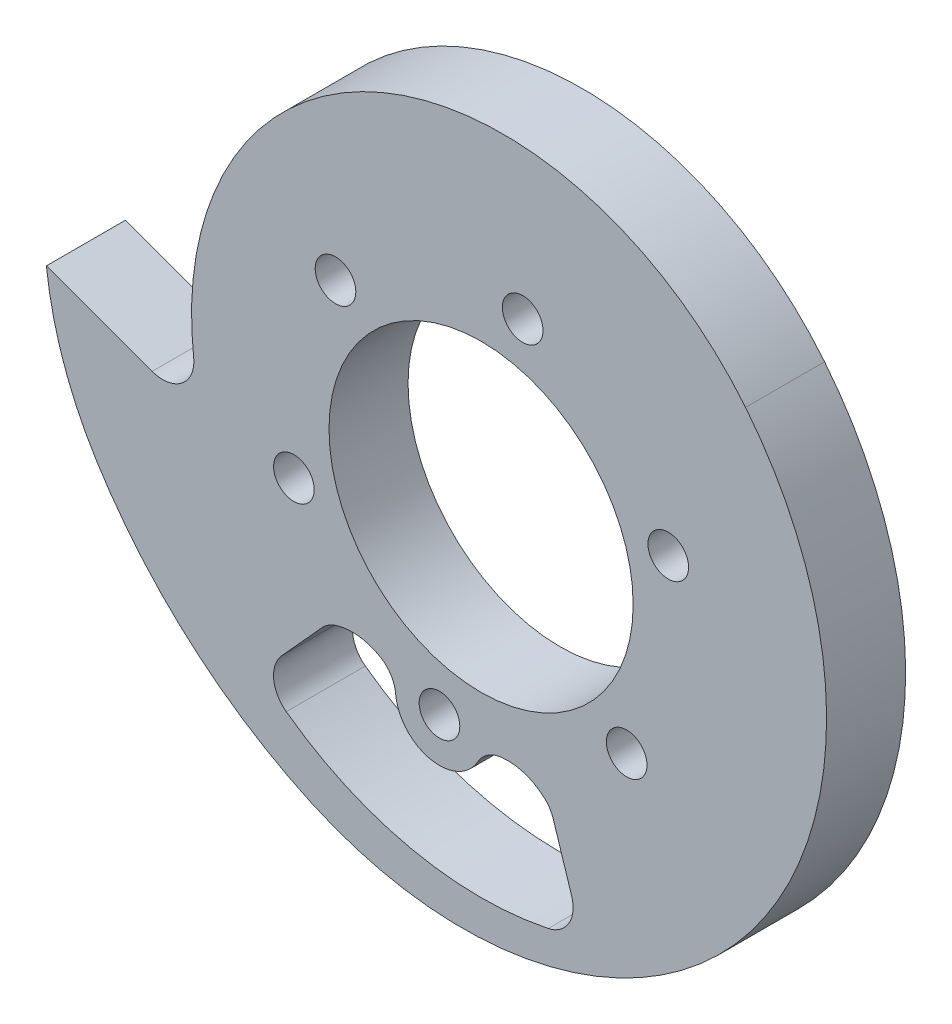
SolidWorks part; units mm, degrees
material "AR500 Weight at A2 Tool Steel Prop."
ref_plane "Front Plane" through (0, 0, 0) normal (0, 0, 1) x (1, 0, 0)
ref_plane "Top Plane" through (0, 0, 0) normal (0, 1, 0) x (1, 0, 0)
ref_plane "Right Plane" through (0, 0, 0) normal (1, 0, 0) x (0, 0, -1)
other "Center of Mass"
sketch "Sketch1" plane through (0, 0, 0) normal (0, 0, 1) x (1, 0, 0)
  line L0 (-69.85, 0) -> (-44.4783, -9.2345)
  line L1 (0, 0) -> (-61.8777, -22.9731) construction
  line L2 (-44.4783, -9.2345) -> (0, 0) construction
  line L3 (-27.2394, -53.4604) -> (0, 0) construction
  line L4 (42.4942, 36.4725) -> (0, 0) construction
  line L5 (0, 0) -> (-25.1554, 0) construction
  line L7 (-69.85, 0) -> (-69.5019, -2.1981) construction
  line L8 (-69.85, 0) -> (-69.85, 19.8503) construction
  line L9 (42.4942, 36.4725) -> (53.0039, 45.4929) construction
  circle A0 centre (0, 0) radius 69.85 construction
  circle A1 centre (0, 0) radius 44.45 construction
  circle A3 centre (0, 0) radius 21.4376 construction
  arc A4 (-69.85, 0) -> (-61.8777, -22.9731) centre (-15.0447, 6.1491) ccw
  arc A6 (-27.2394, -53.4604) -> (42.4942, 36.4725) centre (-2.927, -0.3101) ccw
  arc A8 (-44.4783, -9.2345) -> (42.4942, 36.4725) centre (3.5652, 4.9473) cw
  arc A9 (-61.8777, -22.9731) -> (-27.2394, -53.4604) centre (6.0192, 19.2474) ccw
  circle A10 centre (0, 0) radius 24.4376
  point P21 (-69.0678, -4.9384)
  dimension "D1" = 139.7
  dimension "D2" = 25.4
  dimension "D3" = 20
  dimension "D4" = 42.8752
  dimension "D5" = 27
  dimension "D6" = 25.3717
  dimension "D15" = 13.85
  dimension "D12" = 63
  dimension "D17" = 3
  dimension "D7" = 66.0046
  dimension "D8" = 45.4268
  dimension "D9" = 24.3171
  dimension "D10" = 9
  dimension "D11" = 5
  dimension "D13" = 60
  dimension "D14" = 56
  dimension "D16" = 40.639
extrude "Boss-Extrude1" add sketch "Sketch1" along normal mid plane 12.7 contours A1 | A1 A3 | A1 | A4 A9 A6 A8 L0 A10 region at (-57.7432, -6.2083, 0)
fillet "Fillet3" radius 5 1 edges at (-44.4783, -9.2345, 0)
other "Center of Mass Reference Point1"
sketch "Sketch5" plane through (0, 0, 6.35) normal (0, 0, 1) x (1, 0, 0)
  line L0 (0.2837, 1.3097) -> (1.2994, 5.9996) construction
  circle A0 centre (0, 0) radius 24.4376 construction
  circle A1 centre (0, 0) radius 24.4376 construction
  point P0 (-6.6861, -30.8719)
  point P5 (-30.0789, -9.6456)
  point P6 (-23.3928, 21.2263)
  point P7 (6.6861, 30.8719)
  point P8 (30.0789, 9.6456)
  point P9 (23.3928, -21.2263)
  point P10 (0, 0)
  point P11 (-0.8966, -4.1399)
  point P19 (-5.1727, -23.8839)
  dimension "D1" = 7.15
  dimension "D2" = 6
hole_wizard "1/4 Clearance Hole1" positions "Sketch6" profile "Sketch8" hole size "1/4" standard "ANSI Inch" end condition through all
sketch "Sketch6" plane through (0, 0, 6.35) normal (0, 0, 1) x (1, 0, 0)
  point P0 (-6.6861, -30.8719)
  point P3 (-30.0789, -9.6456)
  point P6 (-23.3928, 21.2263)
  point P9 (6.6861, 30.8719)
  point P12 (30.0789, 9.6456)
  point P15 (23.3928, -21.2263)
sketch "Sketch8" plane through (-6.6861, -30.8719, 6.35) normal (1, 0, 0) x (0, -1, 0)
  line L0 (0, 0) -> (0, 12.7)
  line L1 (0, 12.7) -> (3.2639, 12.7)
  line L2 (3.2639, 12.7) -> (3.2639, 0)
  line L5 (3.2639, 0) -> (0, 0)
  line L11 (0, -6.35) -> (0, 107.95) construction
  dimension "Thru Hole Dia." = 6.5278
  dimension "Thru Hole Depth" = 12.7
sketch "Sketch9" plane through (0, 0, 6.35) normal (0, 0, 1) x (1, 0, 0)
  line L0 (-24.8451, -27.4155) -> (-35.5894, -39.2713)
  line L1 (16.152, 74.5785) -> (-13.5514, -62.5708) construction
  line L3 (16.152, -50.4773) -> (11.2758, -35.2384)
  line L4 (-24.8451, -27.4155) -> (0, 0) construction
  line L5 (6.6861, 30.8719) -> (8.1835, 37.7855) construction
  line L6 (-13.6833, -29.8329) -> (-24.8451, -27.4155) construction
  arc A1 (-35.5894, -39.2713) -> (16.152, -50.4773) centre (0, 0) ccw
  circle A2 centre (-6.6861, -30.8719) radius 3.2639 construction
  circle A3 centre (-6.6861, -30.8719) radius 3.2639 construction
  circle A4 centre (6.6861, 30.8719) radius 3.2639 construction
  circle A5 centre (0, 0) radius 24.4376 construction
  circle A6 centre (0, 0) radius 24.4376 construction
  circle A7 centre (-6.6861, -30.8719) radius 7.0739 construction
  arc A8 (-13.6833, -29.8329) -> (0.1139, -32.821) centre (-6.6861, -30.8719) ccw
  arc A9 (-13.6833, -29.8329) -> (-24.8451, -27.4155) centre (-20.6822, -35.1715) ccw
  arc A10 (0.1139, -32.821) -> (11.2758, -35.2384) centre (4.2769, -40.577) cw
  arc A11 (-27.2394, -53.4604) -> (42.4942, 36.4725) centre (-2.927, -0.3101) ccw construction
  arc A12 (-27.2394, -53.4604) -> (42.4942, 36.4725) centre (-2.927, -0.3101) ccw construction
  point P21 (-0.8966, -4.1399)
  dimension "D1" = 3.81
  dimension "16" = 16
extrude "Cut-Extrude1" cut sketch "Sketch9" against normal through all
fillet "Fillet4" radius 5 6 edges at (16.152, -50.4773, 0) (-35.5894, -39.2713, 0) (11.2758, -35.2384, 0) (-24.8451, -27.4155, 0) (-13.6833, -29.8329, 0) (0.1139, -32.821, 0)
other "Center of Mass Reference Point2"
sketch "Sketch11" [suppressed] plane through (0, 0, 6.35) normal (0, 0, 1) x (1, 0, 0)
  line L0 (0, 0) -> (0.0077, 0.0102) construction
  line L1 (-0.8966, -4.1399) -> (0.0077, 0.0102) construction
  dimension "D1" = 0.0077
  dimension "D2" = 0.0102
  dimension "D3" = 0.0128
sketch "Sketch13" plane through (0, 0, 6.35) normal (0, 0, 1) x (1, 0, 0)
  line L0 (0, 0) -> (0.0112, 0.0518) construction
  dimension "D1" = 0.053
